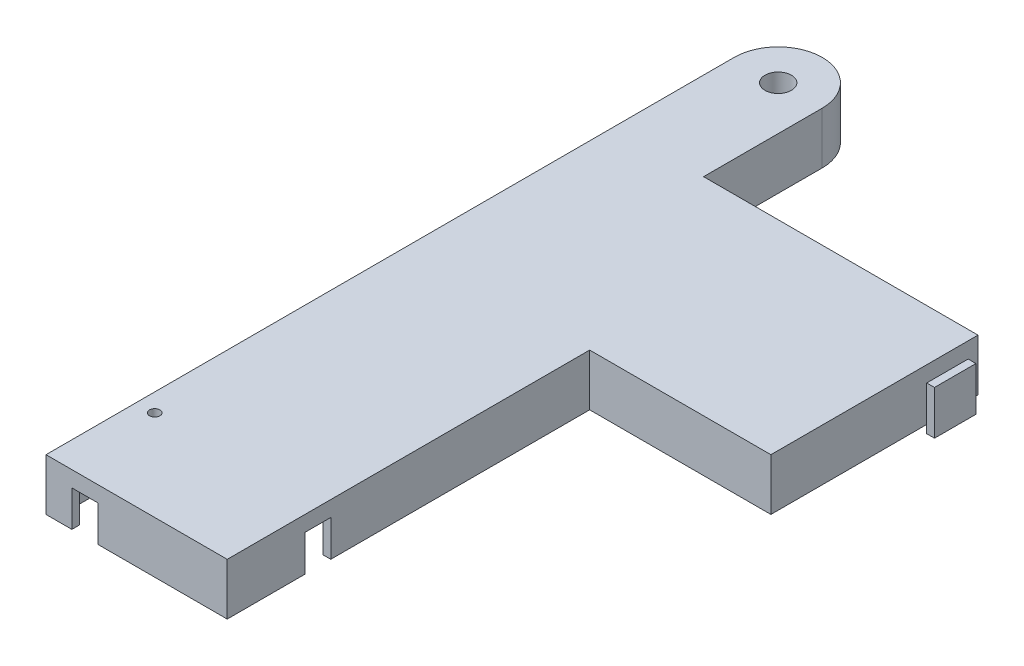
SolidWorks part; units mm, degrees
ref_plane "Front Plane" through (0, 0, 0) normal (0, 0, 1) x (1, 0, 0)
ref_plane "Top Plane" through (0, 0, 0) normal (0, 1, 0) x (1, 0, 0)
ref_plane "Right Plane" through (0, 0, 0) normal (1, 0, 0) x (0, 0, -1)
sketch "CornerrSketch1" plane through (0, 0, 0) normal (0, 1, 0) x (1, 0, 0)
  line L0 (140, 220) -> (140, 140)
  line L2 (0, 0) -> (0, 265.825)
  line L5 (140, 140) -> (70, 140)
  line L6 (70, 140) -> (70, 0)
  line L7 (0, 0) -> (70, 0)
  line L9 (34, 265.825) -> (34, 220)
  line L10 (34, 220) -> (140, 220)
  arc A0 (34, 265.825) -> (0, 265.825) centre (17, 265.825) ccw
  point P2 (17, 282.825)
  point P8 (0, 132.9125)
  dimension "D3" = 34
  dimension "D4" = 80
  dimension "D1" = 220
  dimension "D5" = 45.825
  dimension "D6" = 282.825
  dimension "D7" = 140
  dimension "D11" = 70
extrude "CornerBoss-Extrude1" add sketch "CornerrSketch1" along normal blind 20
shell "Shell2" thickness 3 removed face at (61, 0, -158.5813)
sketch "PadSketch3" plane through (0, 17, 0) normal (0, -1, 0) x (1, 0, 0)
  line L0 (0, -265.825) -> (0, 0) construction
  line L1 (140, -220) -> (34, -220) construction
  circle A0 centre (17, -265.825) radius 12
  circle A1 centre (7, -35) radius 5
  dimension "D1" = 24
  dimension "D2" = 10
  dimension "D3" = 7
  dimension "D4" = 185
extrude "PadBoss-Extrude2" add sketch "PadSketch3" along normal blind 10
sketch "StepperShaftHoleSketch4" plane through (0, 7, 0) normal (0, -1, 0) x (1, 0, 0)
  circle A0 centre (17, -265.825) radius 5.1
  circle A1 centre (7, -35) radius 2
  dimension "D1" = 10.2
  dimension "D2" = 4
extrude "StepperShaftCut-Extrude2" cut sketch "StepperShaftHoleSketch4" against normal through all
sketch "ThreadedNutMountHolesSketch5" plane through (0, 7, 0) normal (0, -1, 0) x (-1, 0, 0)
  circle A8 centre (-17, 273.825) radius 2
  circle A9 centre (-9, 265.825) radius 2
  circle A10 centre (-17, 257.825) radius 2
  circle A11 centre (-25, 265.825) radius 2
  dimension "D1" = 4
  dimension "D2" = 8
  dimension "D3" = 16
  dimension "D5" = 16
extrude "ThreadedNutMountHolesCut-Extrude4" cut sketch "ThreadedNutMountHolesSketch5" against normal blind 10
sketch "TRPegSketch1" plane through (140, 0, 0) normal (1, 0, 0) x (0, 0, -1)
  line L0 (220, 20) -> (220, 0) construction
  line L1 (200.1, 13.9) -> (209.9, 13.9)
  line L2 (200.1, 13.9) -> (200.1, 0)
  line L3 (200.1, 0) -> (209.9, 0)
  line L4 (209.9, 13.9) -> (209.9, 0)
  line L5 (140, 0) -> (220, 0) construction
  point P6 (220, 10)
  dimension "D1" = 10.1
  dimension "D2" = 13.9
  dimension "D3" = 9.8
extrude "TRPegBoss-Extrude1" add sketch "TRPegSketch1" along normal blind 3.1
sketch "TRPegCapSketch2" plane through (143.1, 0, 0) normal (1, 0, 0) x (0, 0, -1)
  line L0 (200.1, 0) -> (209.9, 0) construction
  line L1 (197.1, 17) -> (213.1, 17)
  line L2 (197.1, 17) -> (197.1, 0)
  line L3 (197.1, 0) -> (213.1, 0)
  line L4 (213.1, 17) -> (213.1, 0)
  line L5 (200.1, 13.9) -> (200.1, 0) construction
  dimension "D1" = 16
  dimension "D2" = 3
  dimension "D3" = 17
extrude "TRPegCapBoss-Extrude2" add sketch "TRPegCapSketch2" along normal blind 3
sketch "BottomPegHoleSketch3" plane through (0, 0, 0) normal (0, 0, 1) x (1, 0, 0)
  line L0 (0, 0) -> (70, 0) construction
  line L1 (10, 13.9) -> (20, 13.9)
  line L2 (10, 13.9) -> (10, 0)
  line L3 (10, 0) -> (20, 0)
  line L4 (20, 13.9) -> (20, 0)
  line L5 (0, 20) -> (0, 0) construction
  line L6 (143.1, 13.9) -> (140, 13.9) construction
  dimension "D2" = 10
  dimension "D3" = 10
extrude "BottomPegHoleCut-Extrude1" cut sketch "BottomPegHoleSketch3" against normal blind 3
sketch "BedCenterPegHoleCutSketch1" plane through (70, 0, 0) normal (1, 0, 0) x (0, 0, -1)
  line L0 (0, 0) -> (140, 0) construction
  line L1 (30, 14) -> (40, 14)
  line L2 (30, 14) -> (30, 0)
  line L3 (30, 0) -> (40, 0)
  line L4 (40, 14) -> (40, 0)
  line L5 (140, 20) -> (140, 0) construction
  dimension "D2" = 10
  dimension "D1" = 14
  dimension "D3" = 100
extrude "BedCenterPegHoleCut-Extrude1" cut sketch "BedCenterPegHoleCutSketch1" against normal blind 3
equation "\"RailThickness\"= .125in'Spec"
equation "\"StepperMountingHoleDistance\"= 31mm'Spec"
equation "\"StepperMountingHoleOffsetFromLeftOrRightSide\"= \"StepperMountingHoleOffsetFromItsSide\" + \"RailThickness\""
equation "\"StepperMountingHoleOffsetFromItsSide\"= 5.5mm'Spec"
equation "\"FrontBackRailLength\"= 510mm"
equation "\"DistanceBetweenLeftToRightStepperHoles\"= \"FrontBackRailLength\" - \"StepperMountingHoleOffsetFromLeftOrRightSide\" * 2 - \"StepperMountingHoleDistance\"'Equals 461.65"
equation "\"BedThickness\"= 20mm"
equation "\"BedLLongSide\"= \"BedThirdSize\" * 3'Equals 210"
equation "\"BedLShortSide\"= \"BedThirdSize\" * 2'Equals 140"
equation "\"BedLWidth\"= \"BedThirdSize\"'Equals 70"
equation "\"D4@CornerrSketch1\"=\"BedLWidth\" + \"BedIncreasedByWidth\"/2"
equation "\"D1@CornerrSketch1\" = \"BedLLongSide\" + \"BedIncreasedByWidth\" / 2"
equation "\"BedInnerSquareWidth\"= \"BedThirdSize\" * 3'Equals 210"
equation "\"BedWidth\"= \"BedInnerSquareWidth\" + \"BedLWidth\" * 2 + \"BedIncreasedByWidth\"'Equals 370"
equation "\"BedIncreasedByWidth\"= 20mm"
equation "\"BedIncreasedByLength\"= 0mm"
equation "\"BedThirdSize\"= 70mm"
equation "\"D1@TRPegCapSketch2\"=\"BedPegCapWidth\""
equation "\"StandardWallThickness\"= 3mm"
equation "\"D2@TRPegCapSketch2\" = \"StandardWallThickness\""
equation "\"D3@TRPegCapSketch2\"=\"BedPegCapHeight\""
equation "\"D1@TRPegCapBoss-Extrude2\" = \"StandardWallThickness\""
equation "\"D1@BottomPegHoleCut-Extrude1\"=\"StandardWallThickness\""
equation "\"D1@Shell2\"=\"StandardWallThickness\""
equation "\"D2@TRPegSketch1\"=\"BedPegHeight\""
equation "\"D5@CornerrSketch1\"=\"DistanceFromBedSideToStepperHole\""
equation "\"DistanceFromBedFrontToStepperHole\"= \"LeadScrewNutPadSize\" + 10mm"
equation "\"DistanceFromBedSideToStepperHole\"= ( \"DistanceBetweenLeftToRightStepperHoles\" - \"BedWidth\" ) / 2'Equals 45.825"
equation "\"D7@CornerrSketch1\"= \"BedLShortSide\" + \"BedIncreasedByLength\" / 2"
equation "\"D3@CornerrSketch1\"=\"DistanceFromBedFrontToStepperHole\""
equation "\"BedToBuildPlateStandoffPadSize\"= 10mm"
equation "\"LeadScrewNutPadSize\"= \"LeadScrewNutMountingHoleFlangeDiameter\" + 2mm'Equals 24"
equation "\"D1@PadSketch3\" = \"LeadScrewNutPadSize\""
equation "\"D1@StepperShaftHoleSketch4\"=\"LeadScrewNutInnerShaftFlangeDiameter\""
equation "\"D11@CornerrSketch1\"=\"BedLWidth\""
equation "\"LeadScrewNutInnerShaftFlangeDiameter\"= 10.2mm'Spec"
equation "\"LeadScrewNutMountHoleDiameter\" = \"M3HeatInsertHoleDiameter\"'Spec is 4.1 but smaller for tapping"
equation "\"LeadScrewNutMountingHoleFlangeDiameter\"= 22mm'Spec"
equation "\"LeadScrewNutMountingHoleDistance\"= 16mm'Spec"
equation "\"D2@ThreadedNutMountHolesSketch5\"=\"LeadScrewNutMountingHoleDistance\" / 2"
equation "\"D3@ThreadedNutMountHolesSketch5\"=\"LeadScrewNutMountingHoleDistance\""
equation "\"D5@ThreadedNutMountHolesSketch5\"=\"LeadScrewNutMountingHoleDistance\""
equation "\"D4@ThreadedNutMountHolesSketch5\"=\"LeadScrewNutMountingHoleDistance\"/2"
equation "\"D1@ThreadedNutMountHolesSketch5\"=\"LeadScrewNutMountHoleDiameter\""
equation "\"LeadScrewNutPadDepth\"= \"BedThickness\" / 2'Equals 10"
equation "\"D1@ThreadedNutMountHolesCut-Extrude4\"=\"LeadScrewNutPadDepth\""
equation "\"D2@PadSketch3\"=\"BedToBuildPlateStandoffPadSize\""
equation "\"D3@PadSketch3\"=\"BedToBuildPlateStandoffHolesDistanceFromFront\""
equation "\"BuildPlateWidth\"= 350mm'Spec"
equation "\"D4@PadSketch3\"=\"BedIncreasedByWidth\"/2 + \"BuildPlateWidth\"/2"
equation "\"D2@StepperShaftHoleSketch4\"=\"M3HeatInsertHoleDiameter\""
equation "\"BuildPlateStandoffHolesDistanceFromFront\"= 7mm"
equation "\"BedToBuildPlateStandoffHolesDistanceFromFront\"= \"BuildPlateStandoffHolesDistanceFromFront\" + \"BedIncreasedByLength\" / 2'Equals 7"
equation "\"BedPegHoleWidth\"= 10mm"
equation "\"BedPegHoleHeight\"= \"BedThickness\" - \"StandardWallThickness\" * 2'Equals 14"
equation "\"BedPegWidth\"= \"BedPegHoleWidth\" - .1mm * 2'For easier assembly"
equation "\"BedPegHeight\"= \"BedPegHoleHeight\" - .1mm'For easier assembly"
equation "\"BedTopPegOffsetFromSide\"= 10mm"
equation "\"BedPegBoss\"= \"StandardWallThickness\" + .1mm'For easier assembly"
equation "\"BedPegCapHeight\"= \"BedThickness\" - \"StandardWallThickness\"'Equals 17"
equation "\"BedPegCapWidth\"= \"BedThickness\" / 2 + \"StandardWallThickness\" * 2'Equals 16"
equation "\"D1@TRPegSketch1\"=\"BedTopPegOffsetFromSide\" + .1mm"
equation "\"D3@TRPegSketch1\"= \"BedPegWidth\""
equation "\"D1@TRPegBoss-Extrude1\"=\"BedPegBoss\""
equation "\"D3@BottomPegHoleSketch3\"=\"BedTopPegOffsetFromSide\""
equation "\"D2@BottomPegHoleSketch3\"=\"BedPegHoleWidth\""
equation "\"D1@BedCenterPegHoleCutSketch1\" = \"BedPegHoleHeight\""
equation "\"D2@BedCenterPegHoleCutSketch1\" = \"BedPegHoleWidth\""
equation "\"D3@BedCenterPegHoleCutSketch1\" = \"BedInnerSquareWidth\" / 2 - \"BedPegHoleWidth\" / 2"
equation "\"D1@BedCenterPegHoleCut-Extrude1\"=\"StandardWallThickness\""
equation "\"M3HeatInsertHoleDiameter\"= 4mm'Spec"
